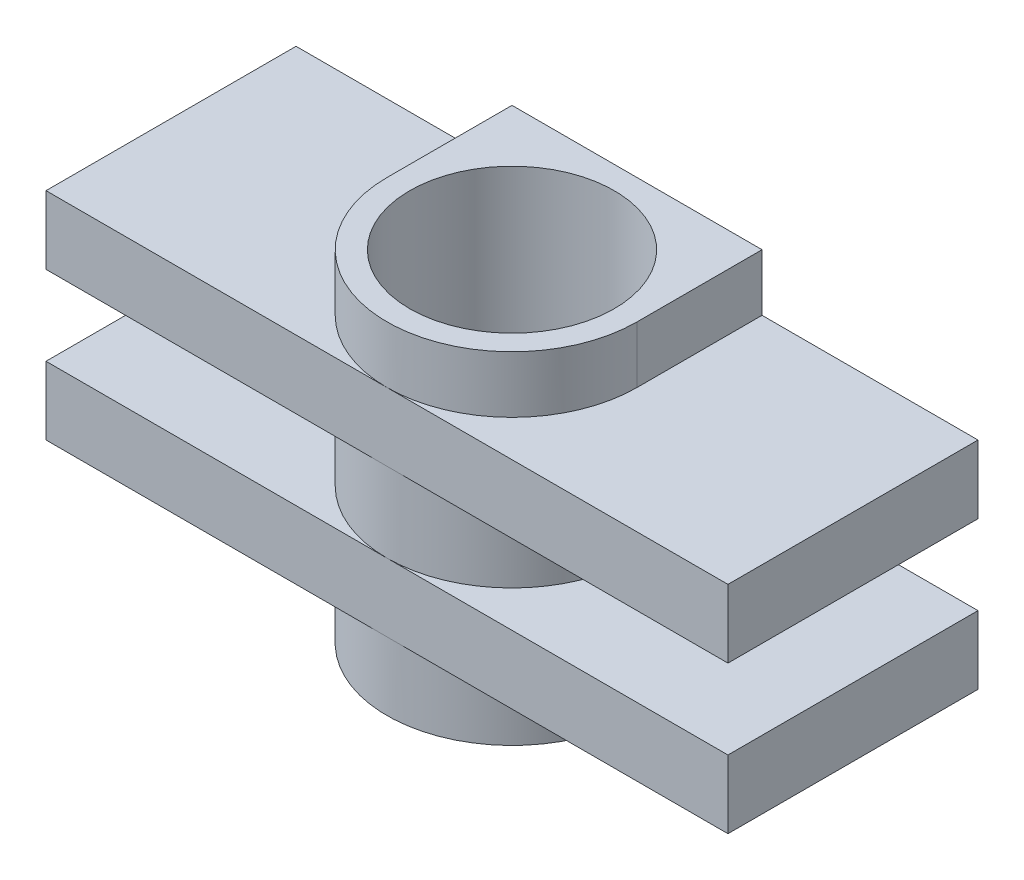
SolidWorks part; units mm, degrees
ref_plane "Alzado" through (0, 0, 0) normal (0, 0, 1) x (1, 0, 0)
ref_plane "Planta" through (0, 0, 0) normal (0, 1, 0) x (1, 0, 0)
ref_plane "Vista lateral" through (0, 0, 0) normal (1, 0, 0) x (0, 0, -1)
sketch "Croquis1" plane through (0, 0, 0) normal (0, 1, 0) x (1, 0, 0)
  line L0 (-5.5, 0) -> (0, 0) construction
  line L1 (0, 0) -> (0, 5.5) construction
  line L2 (-5.5, 0) -> (-5.5, 5.5)
  line L3 (-5.5, 5.5) -> (5.5, 5.5)
  line L4 (5.5, 5.5) -> (5.5, 0)
  arc A1 (-5.5, 0) -> (5.5, 0) centre (0, 0) ccw
  dimension "D2" = 11
extrude "Saliente-Extruir1" add sketch "Croquis1" along normal blind 15
sketch "Croquis2" plane through (0, 15, 0) normal (0, 1, 0) x (1, 0, 0)
  line L0 (5.5, 5.5) -> (-5.5, 5.5) construction
  line L1 (15, 5.5) -> (-15, 5.5)
  line L2 (15, 5.5) -> (15, -5.5)
  line L3 (15, -5.5) -> (-15, -5.5)
  line L4 (-15, 5.5) -> (-15, -5.5)
  line L5 (15, 5.5) -> (-15, -5.5) construction
  line L6 (15, -5.5) -> (-15, 5.5) construction
  point P0 (0, 0)
  dimension "D1" = 30
extrude "Saliente-Extruir2" add sketch "Croquis2" against normal blind 3 from offset 9 offset against normal yes
sketch "Croquis3" plane through (0, 6, 0) normal (0, 1, 0) x (1, 0, 0)
  line L0 (-15, 5.5) -> (-15, -5.5) construction
  line L1 (15, -5.5) -> (-15, -5.5)
  line L2 (15, -5.5) -> (15, 5.5)
  line L3 (15, 5.5) -> (-15, 5.5)
  line L4 (-15, -5.5) -> (-15, 5.5)
  line L5 (15, -5.5) -> (-15, 5.5) construction
  line L6 (15, 5.5) -> (-15, -5.5) construction
  line L7 (15, 5.5) -> (5.5, 5.5) construction
  point P0 (0, 0)
extrude "Saliente-Extruir3" add sketch "Croquis3" along normal blind 3 from offset 3.5
sketch "Croquis4" plane through (0, 15, 0) normal (0, 1, 0) x (1, 0, 0)
  circle A0 centre (0, 0) radius 4.5
  dimension "D1" = 9
extrude "Cortar-Extruir1" cut sketch "Croquis4" against normal through all
fillet "Redondeo6" radius 5.5 1 edges at (-5.5, 7.75, -5.5)
fillet "Redondeo7" radius 5.5 1 edges at (5.5, 7.75, -5.5)
